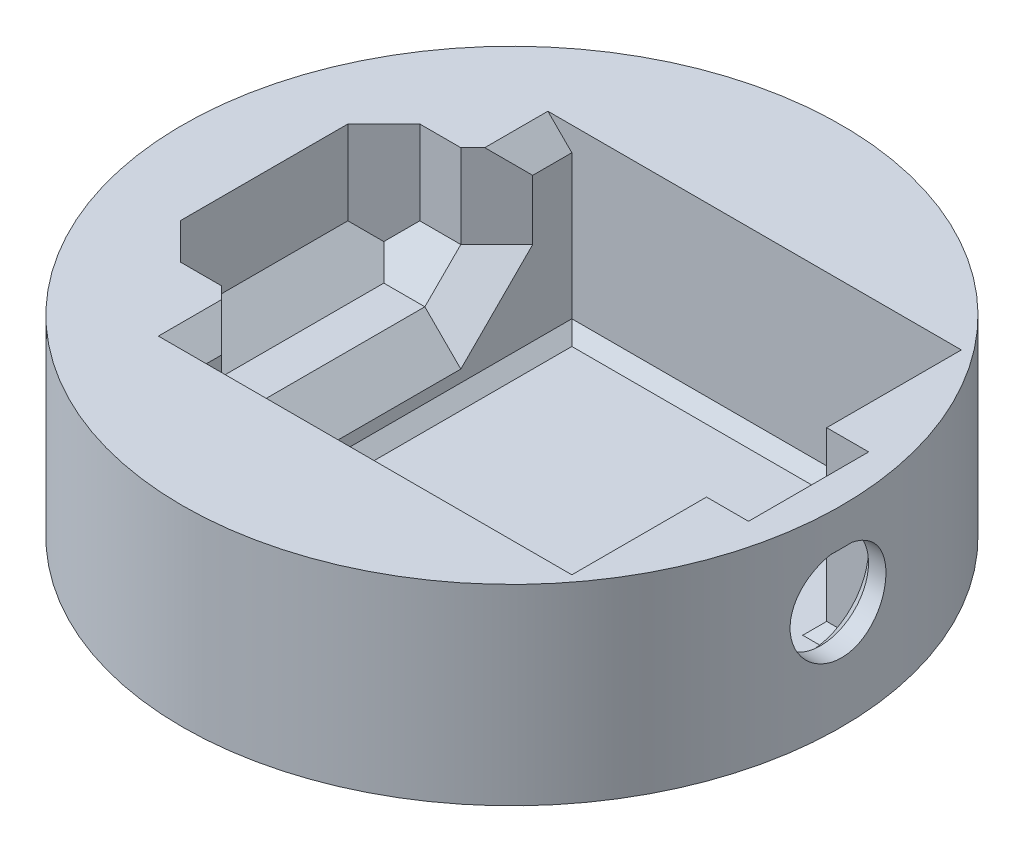
SolidWorks part; units mm, degrees
ref_plane "Front Plane" through (0, 0, 0) normal (0, 0, 1) x (1, 0, 0)
ref_plane "Top Plane" through (0, 0, 0) normal (0, 1, 0) x (1, 0, 0)
ref_plane "Right Plane" through (0, 0, 0) normal (1, 0, 0) x (0, 0, -1)
sketch "Sketch1" plane through (0, 0, 0) normal (0, 1, 0) x (1, 0, 0)
  circle A0 centre (0, 0) radius 27.5
  dimension "D1" = 55
extrude "Boss-Extrude1" add sketch "Sketch1" along normal blind 16
sketch "Sketch3" plane through (0, 16, 0) normal (0, 1, 0) x (1, 0, 0)
  line L0 (21.25, 0) -> (27.5, 0) construction
  line L1 (-11.25, -16.25) -> (16.25, -16.25)
  line L2 (-16.25, -16.25) -> (-16.25, 16.25) construction
  line L3 (-11.25, 16.25) -> (16.25, 16.25) construction
  line L4 (16.25, -16.25) -> (16.25, -1.9281) construction
  line L5 (-11.25, -11.25) -> (0, 0) construction
  line L6 (-11.25, 11.25) -> (0, 0) construction
  line L7 (0, 0) -> (16.25, 0) construction
  line L8 (21.25, 0) -> (27.5, 0) construction
  line L9 (-16.25, 16.25) -> (-11.25, 16.25) construction
  line L10 (16.25, 16.25) -> (21.25, 16.25)
  line L11 (16.25, 0) -> (16.25, -16.25) construction
  line L12 (16.25, -16.25) -> (21.25, -16.25)
  line L13 (21.25, 16.25) -> (21.25, -16.25)
  line L14 (-16.25, 16.25) -> (-11.25, 16.25) construction
  line L15 (-16.25, 16.25) -> (-16.25, -16.25) construction
  line L16 (-16.25, -16.25) -> (-11.25, -16.25) construction
  line L17 (-11.25, 16.25) -> (-11.25, -16.25)
  line L18 (-16.25, 16.25) -> (-11.25, 16.25) construction
  line L19 (-16.25, 16.25) -> (-11.25, 11.25) construction
  line L20 (-16.25, -16.25) -> (-11.25, -11.25) construction
  line L21 (-16.25, -16.25) -> (-11.25, -16.25) construction
  line L22 (0, 0) -> (16.25, 0) construction
  line L23 (16.25, 6.8206) -> (16.25, 16.25) construction
  line L24 (16.25, 16.25) -> (16.25, 0) construction
  line L25 (16.25, 0) -> (21.25, 0) construction
  line L26 (16.25, 0) -> (21.25, 0) construction
  line L27 (0, 0) -> (16.25, 16.25) construction
  line L28 (0, 0) -> (16.25, -16.25) construction
  line L29 (-11.25, 16.25) -> (16.25, 16.25)
  circle A0 centre (0, 0) radius 27.5 construction
  point P1 (0, 0)
  dimension "D1" = 32.5
  dimension "D2" = 32.5
  dimension "D3" = 27.5
  dimension "D5" = 5
  dimension "D6" = 5
extrude "Cut-Extrude1" cut sketch "Sketch3" against normal blind 15
sketch "Sketch4" plane through (21.25, 0, 0) normal (-1, 0, 0) x (0, 0, 1)
  line L0 (0, 5) -> (0, 9) construction
  line L1 (16.25, 1) -> (-16.25, 1) construction
  line L2 (0, 1) -> (0, 5) construction
  line L3 (-2.1032, 12.4024) -> (2.1032, 12.4024)
  arc A0 (-2.1032, 12.4024) -> (2.1032, 12.4024) centre (0, 9) ccw
  arc A1 (2.1032, 12.4024) -> (-2.1032, 12.4024) centre (0, 9) ccw construction
  dimension "D2" = 8
  dimension "D1" = 8
extrude "Cut-Extrude2" cut sketch "Sketch4" against normal blind 15
sketch "Sketch6" plane through (0, 16, 0) normal (0, 1, 0) x (1, 0, 0)
  line L0 (-11.25, 16.25) -> (-11.25, -16.25) construction
  line L1 (-20.6746, 9.9839) -> (-1.8254, 9.9839)
  line L2 (-20.6746, 9.9839) -> (-20.6746, -9.9839)
  line L3 (-20.6746, -9.9839) -> (-1.8254, -9.9839)
  line L4 (-1.8254, 9.9839) -> (-1.8254, -9.9839)
  line L5 (-20.6746, 9.9839) -> (-1.8254, -9.9839) construction
  line L6 (-20.6746, -9.9839) -> (-1.8254, 9.9839) construction
  point P0 (-11.25, 0)
extrude "Cut-Extrude4" cut sketch "Sketch6" against normal blind 10
chamfer "Chamfer2" distance 3 angle 45 6 edges at (-15.9623, 6, 9.9839) (-20.6746, 6, 0) (-15.9623, 6, -9.9839) (-11.25, 11, 9.9839) (-11.25, 11, -9.9839) (-11.25, 6, 0)
chamfer "Chamfer3" distance 3 angle 45 2 edges at (-20.6746, 12.5, -9.9839) (-20.6746, 12.5, 9.9839)
sketch "Sketch8" plane through (0, 16, 0) normal (0, 1, 0) x (1, 0, 0)
  line L0 (21.25, -16.25) -> (21.25, 16.25) construction
  line L1 (17.7452, -5.0134) -> (24.7548, -5.0134)
  line L2 (17.7452, -5.0134) -> (17.7452, 5.0134)
  line L3 (17.7452, 5.0134) -> (24.7548, 5.0134)
  line L4 (24.7548, -5.0134) -> (24.7548, 5.0134)
  line L5 (17.7452, -5.0134) -> (24.7548, 5.0134) construction
  line L6 (17.7452, 5.0134) -> (24.7548, -5.0134) construction
  point P0 (21.25, 0)
extrude "Cut-Extrude5" cut sketch "Sketch8" against normal up to surface (15 mm away) up to face at (5, 1, 0)
chamfer "Chamfer4" distance 1 angle 45 2 edges at (24.7548, 5, 0) (24.7548, 12.4024, 0)
chamfer "Chamfer5" distance 2 angle 45 1 edges at (24.7548, 1, 0)
chamfer "Chamfer6" distance 2 angle 45 2 edges at (-11.25, 16, 14.6169) (-11.25, 16, -14.6169)
chamfer "Chamfer7" distance 1 angle 45 7 edges at (22.0024, 1, -5.0134) (22.0024, 1, 5.0134) (21.25, 1, -10.6317) (5, 1, -16.25) (-11.25, 1, 0) (5, 1, 16.25) (21.25, 1, 10.6317)
chamfer "Chamfer8" distance 0.5 angle 45 1 edges at (27.5, 12.4024, 0)
